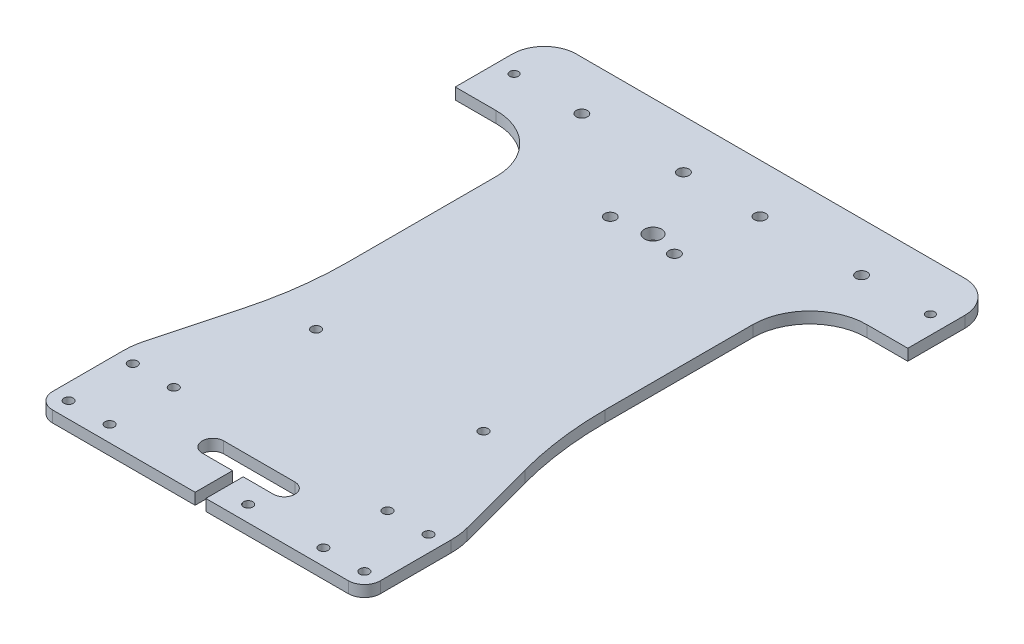
SolidWorks part; units mm, degrees
material "Acrylic (Medium-high impact)"
ref_plane "Front" through (0, 0, 0) normal (0, 0, 1) x (1, 0, 0)
ref_plane "Top" through (0, 0, 0) normal (0, 1, 0) x (1, 0, 0)
ref_plane "Right" through (0, 0, 0) normal (1, 0, 0) x (0, 0, -1)
ref_axis "X" through (-80.9, 0, 0) along (1, 0, 0)
ref_axis "Y" through (0, -50, 0) along (0, 1, 0)
ref_axis "Z" through (0, 0, -80.9) along (0, 0, 1)
sketch "Sketch1" plane through (0, 0, 0) normal (0, 1, 0) x (1, 0, 0)
  line L0 (-46, -160) -> (46, -160)
  line L1 (-46, -160) -> (-46, -133)
  line L2 (-46, -133) -> (-36, -95.6795)
  line L3 (-36, -95.6795) -> (-36, -25)
  line L4 (-36, -25) -> (-63.5, -25)
  line L5 (-63.5, -25) -> (-63.5, 0)
  line L6 (-63.5, 0) -> (63.5, 0)
  line L7 (63.5, 0) -> (63.5, -25)
  line L8 (63.5, -25) -> (36, -25)
  line L9 (36, -25) -> (36, -95.6795)
  line L10 (36, -95.6795) -> (46, -133)
  line L11 (46, -133) -> (46, -160)
  line L12 (0, -160) -> (0, 0) construction
  dimension "D1" = 92
  dimension "D2" = 72
  dimension "D3" = 27
  dimension "D4" = 15
  dimension "D5" = 25
  dimension "D6" = 127
  dimension "D7" = 160
extrude "Boss-Extrude1" add sketch "Sketch1" along normal mid plane 3.175
hole_wizard "M2 Clearance Hole1" positions "Sketch2" profile "Sketch3" hole size "M2" standard "ANSI Metric" end condition up to next
sketch "Sketch2" plane through (0, 1.5875, 0) normal (0, 1, 0) x (1, 0, 0)
  line L0 (-41.5, -155.5) -> (41.5, -155.5) construction
  line L2 (-46, -160) -> (46, -160) construction
  line L3 (-46, -133) -> (-46, -160) construction
  line L4 (46, -160) -> (46, -133) construction
  line L5 (-41.5, -137.5) -> (-41.5, -155.5) construction
  line L8 (41.5, -137.5) -> (41.5, -155.5) construction
  line L9 (-41.5, -137.5) -> (-30, -137.5) construction
  line L10 (-30, -137.5) -> (-30, -155.5) construction
  line L13 (41.5, -137.5) -> (30, -137.5) construction
  line L14 (30, -137.5) -> (30, -155.5) construction
  point P0 (-41.5, -155.5)
  point P2 (41.5, -155.5)
  point P15 (-41.5, -137.5)
  point P17 (41.5, -137.5)
  point P25 (-30, -137.5)
  point P27 (-30, -155.5)
  point P29 (30, -137.5)
  point P31 (30, -155.5)
  dimension "D1" = 4.5
  dimension "D2" = 4.5
  dimension "D3" = 4.5
  dimension "D4" = 18
  dimension "D5" = 60
sketch "Sketch3" plane through (-41.5, 1.5875, 155.5) normal (1, 0, 0) x (0, 0, 1)
  line L0 (0, 0) -> (0, 3.175)
  line L1 (0, 3.175) -> (1.3, 3.175)
  line L2 (1.3, 3.175) -> (1.3, 0)
  line L5 (1.3, 0) -> (0, 0)
  line L11 (0, -6.35) -> (0, 107.95) construction
  dimension "Thru Hole Dia." = 2.6
  dimension "Thru Hole Depth" = 3.175
fillet "Fillet1" radius 4.5 2 edges at (46, 0, 160) (-46, 0, 160)
sketch "Sketch4" plane through (0, 1.5875, 0) normal (0, 1, 0) x (1, 0, 0)
  line L0 (-1.5, -160) -> (-1.5, -149.5)
  line L1 (-41.5, -160) -> (41.5, -160) construction
  line L2 (1.5, -160) -> (1.5, -149.5)
  line L3 (0, 0) -> (0, -146.5) construction
  line L4 (63.5, 0) -> (-63.5, 0) construction
  line L5 (-41.5, -137.5) -> (-41.5, -155.5) construction
  line L6 (-41.5, -146.5) -> (0, -146.5) construction
  line L7 (-1.5, -160) -> (1.5, -160)
  line L8 (-10, -146.5) -> (10, -146.5) construction
  line L9 (-10, -143.5) -> (10, -143.5)
  line L10 (-10, -149.5) -> (-1.5, -149.5)
  line L11 (1.5, -149.5) -> (10, -149.5)
  arc A1 (-10, -143.5) -> (-10, -149.5) centre (-10, -146.5) ccw
  arc A2 (10, -149.5) -> (10, -143.5) centre (10, -146.5) ccw
  point P17 (0, -146.5)
  dimension "D2" = 3
  dimension "D1" = 3
  dimension "D3" = 20
extrude "Cut-Extrude1" cut sketch "Sketch4" against normal up to next
hole_wizard "M2 Clearance Hole3" positions "Sketch5" profile "Sketch6" hole size "M2" standard "ANSI Metric" end condition up to next
sketch "Sketch5" plane through (0, 1.5875, 0) normal (0, 1, 0) x (1, 0, 0)
  line L0 (-24.13, -104.7) -> (24.13, -104.7) construction
  line L2 (-24.13, -104.7) -> (-24.13, -103.43) construction
  line L4 (8.89, -155.5) -> (8.89, -104.7) construction
  line L6 (0, -104.7) -> (0, 0) construction
  line L7 (63.5, 0) -> (-63.5, 0) construction
  line L9 (1.5, -160) -> (41.5, -160) construction
  point P2 (24.13, -104.7)
  point P4 (8.89, -155.5)
  point P20 (-24.13, -103.43)
  dimension "D1" = 48.26
  dimension "D2" = 1.27
  dimension "D3" = 15.24
  dimension "D4" = 50.8
  dimension "D5" = 4.5
sketch "Sketch6" plane through (24.13, 1.5875, 104.7) normal (1, 0, 0) x (0, 0, 1)
  line L0 (0, 0) -> (0, 3.175)
  line L1 (0, 3.175) -> (1.3, 3.175)
  line L2 (1.3, 3.175) -> (1.3, 0)
  line L5 (1.3, 0) -> (0, 0)
  line L11 (0, -6.35) -> (0, 107.95) construction
  dimension "Thru Hole Dia." = 2.6
  dimension "Thru Hole Depth" = 3.175
fillet "Fillet2" radius 9 2 edges at (63.5, 0, 0) (-63.5, 0, 0)
hole_wizard "M2 Clearance Hole2" positions "Sketch7" profile "Sketch8" hole size "M2" standard "ANSI Metric" end condition up to next
sketch "Sketch7" plane through (0, 1.5875, 0) normal (0, 1, 0) x (1, 0, 0)
  line L0 (-58.42, -13.57) -> (58.42, -13.57) construction
  line L2 (0, 0) -> (0, -13.57) construction
  line L3 (54.5, 0) -> (-54.5, 0) construction
  line L5 (-63.5, -25) -> (-36, -25) construction
  point P0 (-58.42, -13.57)
  point P2 (58.42, -13.57)
  dimension "D1" = 116.84
  dimension "D2" = 11.43
sketch "Sketch8" plane through (-58.42, 1.5875, 13.57) normal (1, 0, 0) x (0, 0, 1)
  line L0 (0, 0) -> (0, 3.175)
  line L1 (0, 3.175) -> (1.2, 3.175)
  line L2 (1.2, 3.175) -> (1.2, 0)
  line L5 (1.2, 0) -> (0, 0)
  line L11 (0, -6.35) -> (0, 107.95) construction
  dimension "Thru Hole Dia." = 2.4
  dimension "Thru Hole Depth" = 3.175
fillet "Fillet3" radius 20 2 edges at (46, 0, 133) (-46, 0, 133)
fillet "Fillet4" radius 100 2 edges at (36, 0, 95.6795) (-36, 0, 95.6795)
fillet "Fillet5" radius 16 2 edges at (36, 0, 25) (-36, 0, 25)
sketch "Sketch9" plane through (0, 1.5875, 0) normal (0, 1, 0) x (1, 0, 0)
  line L0 (-13, -22.46) -> (13, -22.46) construction
  line L1 (-13, -18.46) -> (13, -18.46) construction
  line L2 (-13, -26.46) -> (13, -26.46) construction
  line L3 (0, 0) -> (0, -22.46) construction
  line L4 (54.5, 0) -> (-54.5, 0) construction
  line L5 (-63.5, -25) -> (-52, -25) construction
  arc A0 (-13, -18.46) -> (-13, -26.46) centre (-13, -22.46) ccw construction
  arc A1 (13, -26.46) -> (13, -18.46) centre (13, -22.46) ccw construction
  point P2 (0, -22.46)
  dimension "D1" = 2.54
  dimension "D2" = 26
  dimension "D3" = 8
extrude "Cut-Extrude2" [suppressed] cut sketch "Sketch9" against normal up to next
hole_wizard "M4 Clearance Hole1" positions "Sketch10" profile "Sketch11" hole size "M4" standard "ANSI Metric"
sketch "Sketch10" plane through (0, 1.5875, 0) normal (0, 1, 0) x (1, 0, 0)
  line L0 (0, 0) -> (0, -33) construction
  line L1 (54.5, 0) -> (-54.5, 0) construction
  point P0 (0, -33)
  dimension "D1" = 33
sketch "Sketch11" plane through (0, 1.5875, 33) normal (1, 0, 0) x (0, 0, 1)
  line L0 (0, 0) -> (0, 11.5421)
  line L1 (0, 11.5421) -> (2.4, 10.1)
  line L2 (2.4, 10.1) -> (2.4, 0)
  line L5 (2.4, 0) -> (0, 0)
  line L10 (0, 11.5421) -> (-2.4, 10.1) construction
  line L11 (0, -6.35) -> (0, 107.95) construction
  dimension "Hole Dia." = 4.8
  dimension "Hole Depth" = 10.1
  dimension "Drill Angle" = 118
sketch "Sketch12" plane through (0, 1.5875, 0) normal (0, 1, 0) x (1, 0, 0)
  circle A0 centre (7.8, -34.8) radius 1.575 construction
  circle A1 centre (-10.2, -34.8) radius 1.575 construction
  circle A2 centre (7.8, -34.8) radius 1.575
  circle A3 centre (-10.2, -34.8) radius 1.575
  circle A4 centre (39.25, -13.725) radius 1.575 construction
  circle A5 centre (10.75, -13.725) radius 1.575 construction
  circle A6 centre (-10.75, -13.725) radius 1.575 construction
  circle A7 centre (-39.25, -13.725) radius 1.575 construction
  circle A8 centre (39.25, -13.725) radius 1.575
  circle A9 centre (10.75, -13.725) radius 1.575
  circle A10 centre (-10.75, -13.725) radius 1.575
  circle A11 centre (-39.25, -13.725) radius 1.575
extrude "Cut-Extrude3" cut sketch "Sketch12" against normal through all
